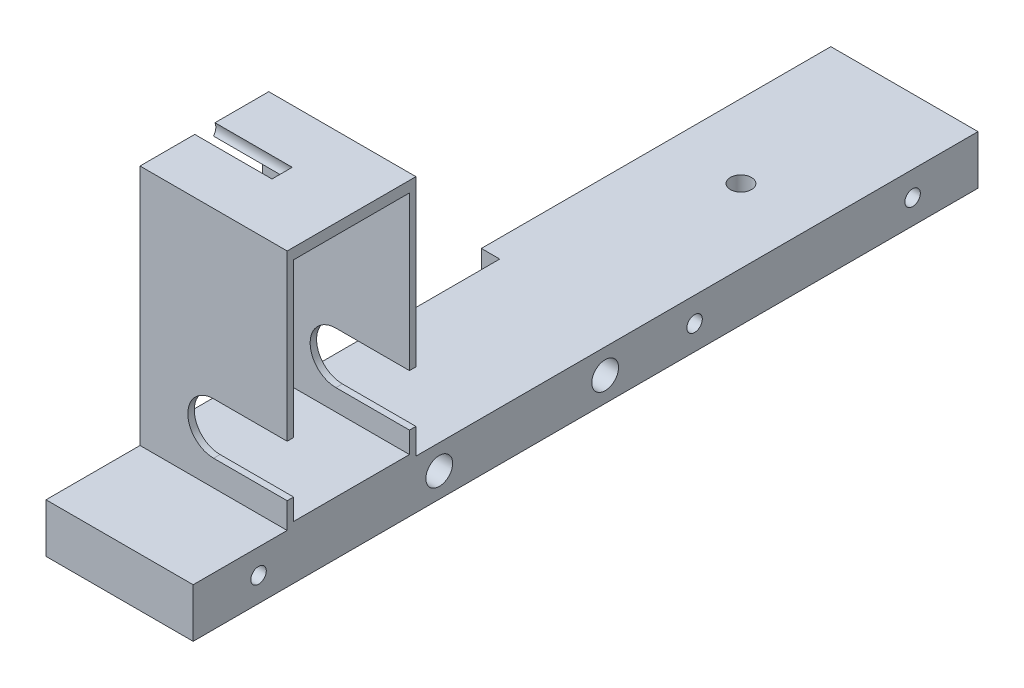
SolidWorks part; units mm, degrees
material "TPU"
ref_plane "Front Plane" through (0, 0, 0) normal (0, 0, 1) x (1, 0, 0)
ref_plane "Top Plane" through (0, 0, 0) normal (0, 1, 0) x (1, 0, 0)
ref_plane "Right Plane" through (0, 0, 0) normal (1, 0, 0) x (0, 0, -1)
sketch "Sketch2" plane through (0, 0, 0) normal (0, 1, 0) x (1, 0, 0)
  line L0 (0, 0) -> (0, 152.4)
  line L1 (0, 152.4) -> (28.575, 152.4)
  line L2 (28.575, 152.4) -> (28.575, 0)
  line L3 (28.575, 0) -> (0, 0)
  dimension "D1" = 152.4
  dimension "D2" = 28.575
extrude "Boss-Extrude1" add sketch "Sketch2" along normal blind 9.525
sketch "Sketch3" plane through (0, 0, 0) normal (-1, 0, 0) x (0, 0, 1)
  line L3 (-152.4, 9.525) -> (0, 9.525) construction
  line L4 (-152.4, 9.525) -> (-152.4, 0) construction
  point P6 (-139.7, 4.7625)
  point P14 (-139.7, 4.7625)
  dimension "D1" = 4.7625
  dimension "D2" = 12.7
sketch "Sketch8" plane through (0, 0, 0) normal (-1, 0, 0) x (0, 0, 1)
  point P0 (-139.7, 4.7625)
hole_wizard "Ø3.0mm Dowel Hole1" positions "Sketch8" profile "Sketch9" hole size "Ø3.0" standard "ANSI Metric" end condition through all
sketch "Sketch9" plane through (0, 4.7625, -139.7) normal (0, 1, 0) x (0, 0, 1)
  line L0 (0, 0) -> (0, 28.575)
  line L1 (0, 28.575) -> (1.5, 28.575)
  line L2 (1.5, 28.575) -> (1.5, 0)
  line L5 (1.5, 0) -> (0, 0)
  line L11 (0, -6.35) -> (0, 107.95) construction
  dimension "Thru Hole Dia." = 3
  dimension "Thru Hole Depth" = 28.575
pattern_linear "LPattern1" count 4 spacing 42.3333 along (0, 0, 1) skipping (2, 0) of "Ø3.0mm Dowel Hole1"
sketch "Sketch12" plane through (0, 9.525, 0) normal (0, 1, 0) x (1, 0, 0)
  line L0 (28.575, 0) -> (28.575, 152.4) construction
  line L2 (0, 0) -> (28.575, 0) construction
  circle A1 centre (14.2875, 31.75) radius 10.975
  circle A2 centre (14.2875, 120.65) radius 2.05
  point P0 (14.2875, 120.65)
  point P1 (14.2875, 76.2)
  point P2 (14.2875, 31.75)
  dimension "D8" = 4.1
  dimension "D9" = 21.95
  dimension "D1" = 14.2875
  dimension "D2" = 14.2875
  dimension "D3" = 14.2875
  dimension "D4" = 76.2
  dimension "D5" = 44.45
  dimension "D6" = 44.45
sketch "Sketch13" plane through (0, 0, 0) normal (-1, 0, 0) x (0, 0, 1)
  line L2 (0, 9.525) -> (0, 0) construction
  line L3 (-152.4, 9.525) -> (0, 9.525) construction
  circle A0 centre (-80, 4.7625) radius 2.6
  circle A1 centre (-47.79, 4.7625) radius 2.6
  point P5 (-80, 4.7625)
  point P11 (-47.79, 4.7625)
  dimension "D1" = 80
  dimension "D2" = 4.7625
  dimension "D3" = 32.21
extrude "Cut-Extrude1" cut sketch "Sketch12" against normal through all contours A2
extrude "Cut-Extrude2" cut sketch "Sketch12<4>" against normal blind 4 contours A1
sketch "Sketch12<4>" plane through (0, 9.525, 0) normal (0, 1, 0) x (1, 0, 0) same geometry as "Sketch12"
sketch "Sketch15" plane through (0, 5.525, 0) normal (0, 1, 0) x (1, 0, 0)
  circle A0 centre (14.2875, 31.75) radius 2.5
  dimension "D1" = 5
extrude "Cut-Extrude3" cut sketch "Sketch15" against normal through all
extrude "Cut-Extrude4" cut sketch "Sketch13" against normal through all
sketch "Sketch17" plane through (0, 0, 0) normal (-1, 0, 0) x (0, 0, 1)
  line L0 (-152.4, 9.525) -> (0, 9.525) construction
  line L1 (-84.535, 9.525) -> (-43.255, 9.525)
  line L2 (-84.535, 9.525) -> (-84.535, 0)
  line L3 (-84.535, 0) -> (-43.255, 0)
  line L4 (-43.255, 9.525) -> (-43.255, 0)
  line L5 (-152.4, 0) -> (0, 0) construction
  circle A3 centre (-80, 4.7625) radius 2.6 construction
  circle A4 centre (-47.79, 4.7625) radius 2.6 construction
  point P12 (-84.535, 4.7625)
  dimension "D2" = 41.28
  dimension "D1" = 32.21
  dimension "D4" = 4.535
  dimension "D3" = 4.535
extrude "Cut-Extrude5" cut sketch "Sketch17" against normal offset from surface (3.575 mm away) 25 up to face at (28.575, 4.7625, -77.4)
sketch "Sketch18" plane through (0, 9.525, 0) normal (0, 1, 0) x (1, 0, 0)
  line L0 (0, 43.255) -> (0, 0) construction
  line L1 (0, 18.255) -> (28.575, 18.255)
  line L2 (0, 18.255) -> (0, 43.255)
  line L3 (0, 43.255) -> (28.575, 43.255)
  line L4 (28.575, 18.255) -> (28.575, 43.255)
  line L5 (28.575, 0) -> (28.575, 152.4) construction
  point P8 (0, 20.0067)
  dimension "D1" = 25
extrude "Boss-Extrude3" add sketch "Sketch18" along normal blind 47
sketch "Sketch19" plane through (0, 0, 0) normal (-1, 0, 0) x (0, 0, 1)
  line L1 (-42.005, 54.4135) -> (-19.505, 54.4135)
  line L2 (-42.005, 54.4135) -> (-42.005, 10.4135)
  line L3 (-42.005, 10.4135) -> (-19.505, 10.4135)
  line L4 (-19.505, 54.4135) -> (-19.505, 10.4135)
  dimension "D1" = 22.5
  dimension "D2" = 44
extrude "Cut-Extrude12" cut sketch "Sketch19" against normal up to next
sketch "Sketch20" plane through (0, 0, 0) normal (-1, 0, 0) x (0, 0, 1)
  line L1 (-43.255, 55.8874) -> (-18.255, 55.8874) construction
  line L2 (-43.255, 0) -> (-43.255, 56.525) construction
  line L3 (-18.255, 56.525) -> (-18.255, 9.525) construction
  line L5 (-43.255, 56.525) -> (-18.255, 56.525) construction
  line L8 (-32.8156, 56.525) -> (-28.8877, 56.525)
  arc A0 (-28.8877, 56.525) -> (-32.8156, 56.525) centre (-30.8517, 55.7137) cw
extrude "Cut-Extrude18" cut sketch "Sketch20" against normal blind 15
sketch "Sketch21" plane through (0, 0, -18.255) normal (0, 0, 1) x (1, 0, 0)
  line L0 (14.2875, 9.525) -> (14.2875, 14.525) construction
  line L1 (0, 9.525) -> (28.575, 9.525) construction
  line L3 (14.2875, 24.525) -> (28.575, 24.525)
  line L4 (28.575, 56.525) -> (28.575, 9.525) construction
  line L5 (28.575, 24.525) -> (28.575, 14.525)
  line L6 (28.575, 14.525) -> (14.2875, 14.525)
  arc A0 (14.2875, 14.525) -> (14.2875, 24.525) centre (14.2875, 19.525) cw
  dimension "D2" = 5
  dimension "D1" = 5
extrude "Cut-Extrude17" cut sketch "Sketch21" against normal blind 25
